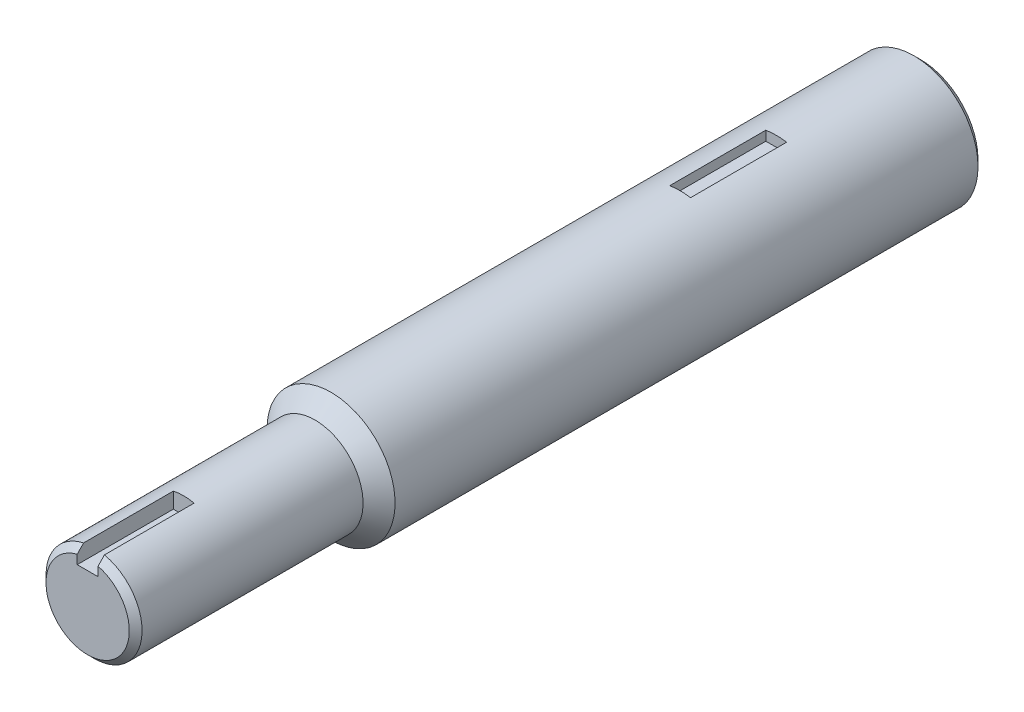
SolidWorks part; units mm, degrees
ref_plane "Front Plane" through (0, 0, 0) normal (0, 0, 1) x (1, 0, 0)
ref_plane "Top Plane" through (0, 0, 0) normal (0, 1, 0) x (1, 0, 0)
ref_plane "Right Plane" through (0, 0, 0) normal (1, 0, 0) x (0, 0, -1)
sketch "Sketch1" plane through (0, 0, 0) normal (0, 1, 0) x (1, 0, 0)
  line L0 (10, 35) -> (7.5, 35)
  line L1 (10, 130) -> (0, 130)
  line L2 (10, 130) -> (10, 35)
  line L3 (7.5, 0) -> (0, 0)
  line L4 (0, 130) -> (0, 0)
  line L5 (10, 130) -> (0, 0) construction
  line L6 (12.772, 0) -> (0, 130) construction
  line L7 (7.5, 35) -> (7.5, 0)
  point P0 (5.6086, 72.9124)
  dimension "D1" = 10
  dimension "D2" = 130
  dimension "D3" = 7.5
  dimension "D4" = 35
revolve "Revolve1" add sketch "Sketch1" angle 360 about L4
chamfer "Chamfer1" distance 1 angle 45 2 edges at (-10, 0, -130) (-7.5, 0, 0)
ref_axis "Axis1" through (0, 0, -35) along (0, 0, -1)
ref_plane "Plane2" through (0, 0, -107.5) normal (0, 0, -1) x (-1, 0, 0)
sketch "Sketch3" plane through (0, 0, -107.5) normal (0, 0, -1) x (-1, 0, 0)
  line L1 (-1.625, 11.625) -> (1.625, 11.625)
  line L2 (-1.625, 11.625) -> (-1.625, 8.375)
  line L3 (-1.625, 8.375) -> (1.625, 8.375)
  line L4 (1.625, 11.625) -> (1.625, 8.375)
  line L5 (-1.625, 11.625) -> (1.625, 8.375) construction
  line L6 (-1.625, 8.375) -> (1.625, 11.625) construction
  circle A0 centre (0, 0) radius 10 construction
  point P0 (0, 10)
  dimension "D1" = 3.25
extrude "Cut-Extrude2" cut sketch "Sketch3" against normal blind 15
sketch "Sketch4" plane through (0, 0, 0) normal (0, 0, 1) x (1, 0, 0)
  line L1 (-1.625, 8.125) -> (1.625, 8.125)
  line L2 (-1.625, 8.125) -> (-1.625, 4.875)
  line L3 (-1.625, 4.875) -> (1.625, 4.875)
  line L4 (1.625, 8.125) -> (1.625, 4.875)
  line L5 (-1.625, 8.125) -> (1.625, 4.875) construction
  line L6 (-1.625, 4.875) -> (1.625, 8.125) construction
  circle A1 centre (0, 0) radius 6.5 construction
  point P0 (0, 6.5)
  dimension "D1" = 3.25
extrude "Cut-Extrude3" cut sketch "Sketch4" against normal blind 15
chamfer "Chamfer2" distance 3 angle 45 1 edges at (-10, 0, -35)
